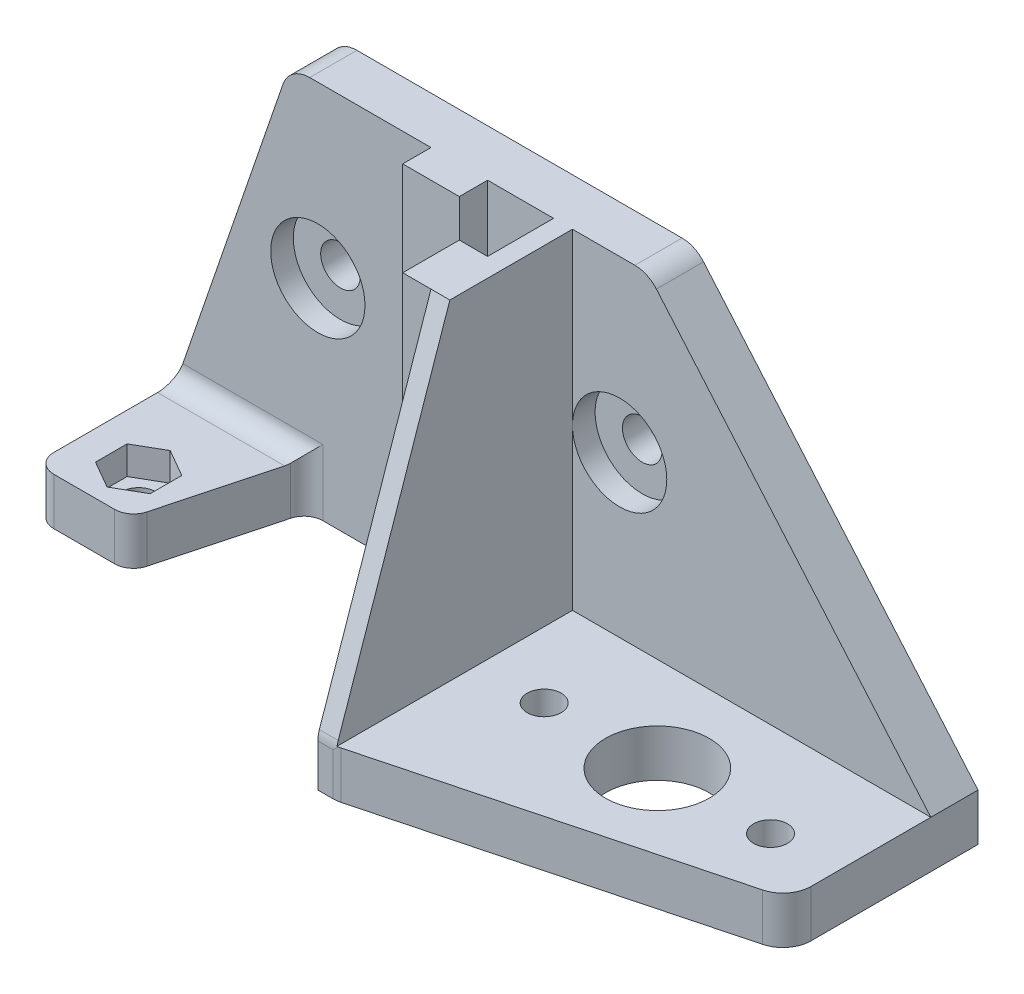
SolidWorks part; units mm, degrees
ref_plane "Front Plane" through (0, 0, 0) normal (0, 0, 1) x (1, 0, 0)
ref_plane "Top Plane" through (0, 0, 0) normal (0, 1, 0) x (1, 0, 0)
ref_plane "Right Plane" through (0, 0, 0) normal (1, 0, 0) x (0, 0, -1)
sketch "Sketch1" plane through (0, 0, 0) normal (0, 1, 0) x (1, 0, 0)
  line L1 (0, 0) -> (-80, 0)
  line L2 (0, 0) -> (0, 30)
  line L3 (0, 30) -> (-80, 30)
  line L4 (-80, 0) -> (-80, 30)
  dimension "D1" = 80
  dimension "D2" = 30
extrude "Boss-Extrude1" add sketch "Sketch1" along normal blind 5
sketch "Sketch2" plane through (0, 5, 0) normal (0, 1, 0) x (1, 0, 0)
  line L0 (-80, 0) -> (0, 0) construction
  line L1 (-60, 0) -> (-40, 0)
  line L2 (-60, 0) -> (-60, 25)
  line L3 (-60, 25) -> (-40, 25)
  line L4 (-40, 0) -> (-40, 25)
  line L5 (0, 0) -> (0, 30) construction
  dimension "D1" = 20
  dimension "D2" = 25
  dimension "D3" = 40
extrude "Cut-Extrude1" cut sketch "Sketch2" against normal through all
sketch "Sketch3" plane through (0, 5, 0) normal (0, 1, 0) x (1, 0, 0)
  line L0 (-80, 30) -> (0, 30)
  line L1 (0, 30) -> (0, 25)
  line L2 (0, 0) -> (0, 30) construction
  line L3 (0, 25) -> (-38, 25)
  line L4 (-38, 25) -> (-38, 0)
  line L5 (-40, 0) -> (0, 0) construction
  line L6 (-38, 0) -> (-40, 0)
  line L7 (-40, 0) -> (-40, 25)
  line L8 (-40, 25) -> (-80, 25)
  line L9 (-80, 30) -> (-80, 0) construction
  line L10 (-80, 25) -> (-80, 30)
  line L12 (-40, 25) -> (-60, 25) construction
  dimension "D1" = 2
extrude "Boss-Extrude2" add sketch "Sketch3" along normal blind 35
sketch "Sketch4" plane through (0, 5, 0) normal (0, 1, 0) x (1, 0, 0)
  line L1 (-40, 0) -> (-40, 25) construction
  line L2 (-38, 25) -> (0, 25) construction
  circle A0 centre (-19, 15) radius 5.5
  circle A1 centre (-7, 15) radius 1.8
  circle A2 centre (-31, 15) radius 1.8
  dimension "D1" = 3.6
  dimension "D2" = 3.6
  dimension "D3" = 11
  dimension "D4" = 12
  dimension "D5" = 12
  dimension "D6" = 21
  dimension "D7" = 10
  dimension "D8" = 10
  dimension "D9" = 10
extrude "Cut-Extrude2" cut sketch "Sketch4" against normal through all
chamfer "Chamfer1" distance 38 distance2 10 1 edges at (0, 2.5, 0) first distance on face at (-29.1667, 17.9167, 0)
fillet "Fillet1" radius 3 1 edges at (0, 2.5, -10)
sketch "Sketch5" plane through (0, 0, -30) normal (0, 0, -1) x (-1, 0, 0)
  line L0 (0, 40) -> (80, 40) construction
  line L1 (38, 40) -> (38, 5) construction
  line L2 (40, 0) -> (40, 40) construction
  circle A0 centre (33, 22) radius 2.1
  circle A1 centre (65, 22) radius 2.1
  dimension "D1" = 4.2
  dimension "D2" = 4.2
  dimension "D3" = 18
  dimension "D4" = 18
  dimension "D5" = 5
  dimension "D6" = 25
extrude "Cut-Extrude3" cut sketch "Sketch5" against normal through all
sketch "Sketch6" plane through (0, 0, -25) normal (0, 0, 1) x (1, 0, 0)
  circle A0 centre (-33, 22) radius 5
  circle A1 centre (-65, 22) radius 5
  dimension "D1" = 10
  dimension "D2" = 10
extrude "Cut-Extrude4" cut sketch "Sketch6" against normal blind 2.4
chamfer "Chamfer2" distance 35 distance2 30 1 edges at (0, 40, -27.5) first distance on face at (0, 17.9167, -21.3803)
fillet "Fillet2" radius 3 1 edges at (-30, 40, -27.5)
sketch "Sketch7" plane through (0, 0, 0) normal (0, -1, 0) x (1, 0, 0)
  line L0 (-40, -25) -> (-60, -25) construction
  line L1 (-53, -25) -> (-47, -25)
  line L2 (-53, -25) -> (-53, -22)
  line L3 (-53, -22) -> (-47, -22)
  line L4 (-47, -25) -> (-47, -22)
  line L5 (-40, 0) -> (-40, -25) construction
  line L6 (-40, -12) -> (-43, -12)
  line L7 (-40, -12) -> (-40, -18)
  line L8 (-40, -18) -> (-43, -18)
  line L9 (-43, -12) -> (-43, -18)
  dimension "D1" = 3
  dimension "D2" = 3
  dimension "D3" = 6
  dimension "D4" = 6
  dimension "D5" = 7
  dimension "D6" = 7
extrude "Boss-Extrude3" add sketch "Sketch7" against normal up to surface (40 mm away) up to face at (-47.345, 40, -20)
chamfer "Chamfer3" distance 35 distance2 12 1 edges at (-39, 40, 0) first distance on face at (-38.8, 20, 0)
fillet "Fillet3" radius 3 2 edges
chamfer "Chamfer4" distance 35 distance2 12 1 edges at (-80, 40, -27.5) first distance on face at (-80, 17.9167, -20.4167)
fillet "Fillet4" radius 3 1 edges at (-68, 40, -27.5)
sketch "Sketch8" plane through (0, 0, 0) normal (0, -1, 0) x (1, 0, 0)
  line L0 (-40, 0) -> (-40, -12) construction
  line L1 (-53, -25) -> (-60, -25) construction
  circle A0 centre (-74, -15) radius 1.8
  dimension "D1" = 3.6
  dimension "D2" = 34
  dimension "D3" = 10
extrude "Cut-Extrude5" cut sketch "Sketch8" against normal through all
sketch "Sketch9" plane through (0, 5, 0) normal (0, 1, 0) x (1, 0, 0)
  line L0 (-80, 10) -> (-70, 10)
  line L1 (-80, 25) -> (-80, 0) construction
  line L2 (-70, 10) -> (-66, 25)
  line L3 (-80, 25) -> (-60, 25) construction
  line L4 (-66, 25) -> (-60, 25)
  line L5 (-60, 25) -> (-60, 0)
  line L6 (-60, 0) -> (-80, 0)
  line L7 (-80, 0) -> (-80, 10)
  dimension "D1" = 10
  dimension "D2" = 6
  dimension "D3" = 10
extrude "Cut-Extrude6" cut sketch "Sketch9" against normal through all
fillet "Fillet5" radius 2 4 edges at (-66, 2.5, -25) (-80, 2.5, -10) (-70, 2.5, -10)
sketch "Sketch10" plane through (0, 5, 0) normal (0, 1, 0) x (1, 0, 0)
  line L1 (-71.1, 13.3257) -> (-71.1, 16.6743)
  line L2 (-71.1, 16.6743) -> (-74, 18.3486)
  line L3 (-74, 18.3486) -> (-76.9, 16.6743)
  line L4 (-76.9, 16.6743) -> (-76.9, 13.3257)
  line L5 (-76.9, 13.3257) -> (-74, 11.6514)
  line L6 (-74, 11.6514) -> (-71.1, 13.3257)
  circle A0 centre (-74, 15) radius 2.9 construction
  dimension "D1" = 5.8
extrude "Cut-Extrude7" cut sketch "Sketch10" against normal blind 3
